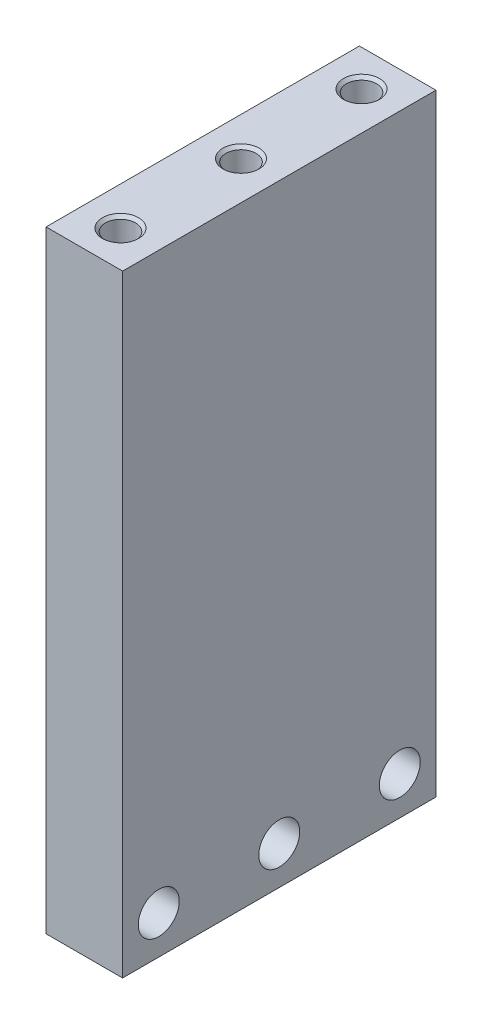
SolidWorks part; units mm, degrees
ref_plane "Front Plane" through (0, 0, 0) normal (0, 0, 1) x (1, 0, 0)
ref_plane "Top Plane" through (0, 0, 0) normal (0, 1, 0) x (1, 0, 0)
ref_plane "Right Plane" through (0, 0, 0) normal (1, 0, 0) x (0, 0, -1)
sketch "Sketch1" plane through (0, 0, 0) normal (0, 0, 1) x (1, 0, 0)
  line L1 (0, 0) -> (6.35, 0)
  line L2 (0, 0) -> (0, 50.8)
  line L3 (0, 50.8) -> (6.35, 50.8)
  line L4 (6.35, 0) -> (6.35, 50.8)
extrude "Boss-Extrude1" add sketch "Sketch1" along normal blind 26
sketch "Sketch4" plane through (6.35, 0, 0) normal (1, 0, 0) x (0, 0, -1)
  line L0 (0, 0) -> (0, 50.8) construction
  line L1 (-26, 0) -> (-26, 50.8) construction
  line L2 (-26, 0) -> (0, 0) construction
  circle A0 centre (-3, 3.175) radius 1.7
  circle A1 centre (-23, 3.175) radius 1.7
  circle A2 centre (-13, 3.175) radius 1.7
  dimension "D1" = 10
  dimension "D2" = 3.4
  dimension "D3" = 3
  dimension "D4" = 3
  dimension "D5" = 3.175
  dimension "D6" = 3.175
extrude "Cut-Extrude3" cut sketch "Sketch4" against normal blind 6.35
sketch "Sketch6" plane through (0, 0, 0) normal (-1, 0, 0) x (0, 0, 1)
  line L0 (26, 0) -> (0, 0) construction
  circle A0 centre (13, 3.175) radius 1.5
  circle A1 centre (3, 3.175) radius 1.7 construction
  dimension "D1" = 3
  dimension "D2" = 10
  dimension "D3" = 3.175
sketch "Sketch9" plane through (0, 50.8, 0) normal (0, 1, 0) x (1, 0, 0)
  line L0 (6.35, 0) -> (0, 0) construction
  line L3 (0, -26) -> (0, 0) construction
  line L4 (0, -11.5) -> (0, -14.5) construction
  circle A6 centre (3.175, -3) radius 1.25
  circle A7 centre (3.175, -13) radius 1.25
  circle A8 centre (3.175, -23) radius 1.25
  point P5 (0, 0)
  point P7 (3.8484, -20.1752)
  dimension "D1" = 3
  dimension "D2" = 10
  dimension "D3" = 10
  dimension "D4" = 20
  dimension "D5" = 3.175
  dimension "D6" = 3.175
sketch "Sketch12" plane through (0, 50.8, 0) normal (0, 1, 0) x (1, 0, 0)
  circle A0 centre (3.175, -3) radius 1.25
  circle A1 centre (3.175, -13) radius 1.25
  circle A2 centre (3.175, -23) radius 1.25
  point P9 (3.175, -14)
  dimension "D1" = 2.5
  dimension "D2" = 2.5
  dimension "D3" = 2.5
sketch "Sketch14" plane through (0, 50.8, 0) normal (0, 1, 0) x (1, 0, 0)
  circle A0 centre (3.175, -23) radius 1.25 construction
  circle A1 centre (3.175, -13) radius 1.25 construction
  circle A2 centre (3.175, -3) radius 1.25 construction
  circle A3 centre (3.175, -23) radius 1.25
  circle A4 centre (3.175, -13) radius 1.25
  circle A5 centre (3.175, -3) radius 1.25
extrude "Cut-Extrude13" cut sketch "Sketch14" against normal blind 5
chamfer "Chamfer3" distance 0.25 angle 45 3 edges at (3.175, 50.8, 24.25) (3.175, 50.8, 14.25) (3.175, 50.8, 4.25)
